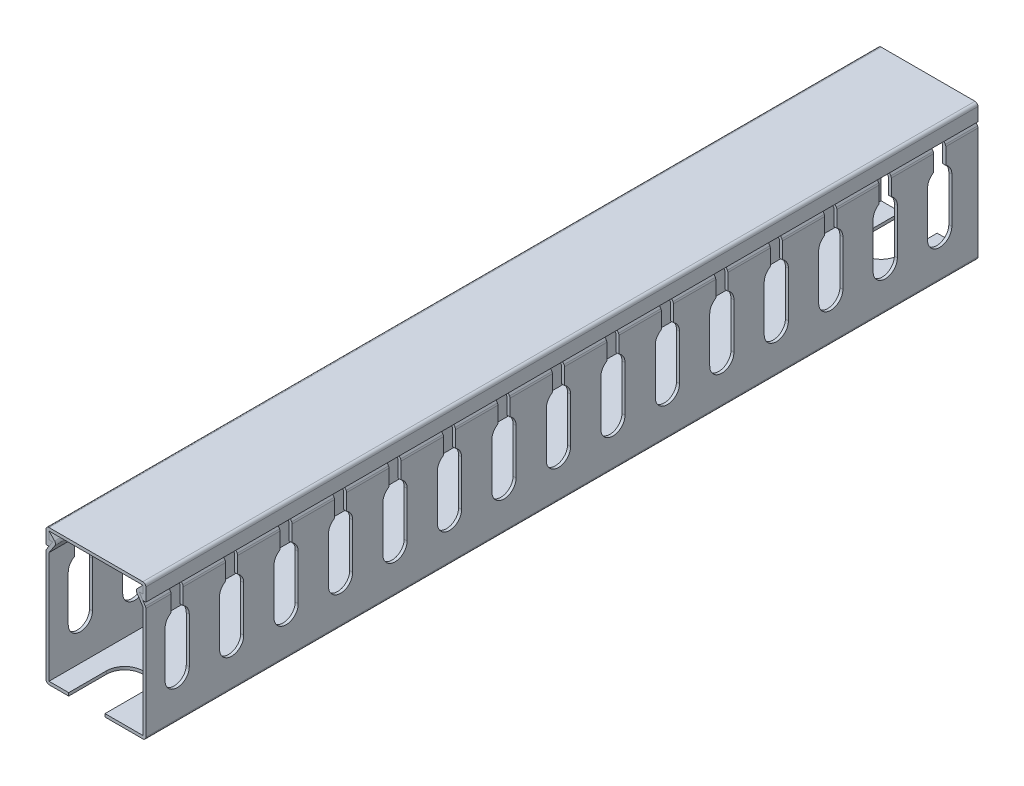
SolidWorks part; units mm, degrees
ref_plane "Front Plane" through (0, 0, 0) normal (0, 0, 1) x (1, 0, 0)
ref_plane "Top Plane" through (0, 0, 0) normal (0, 1, 0) x (1, 0, 0)
ref_plane "Right Plane" through (0, 0, 0) normal (1, 0, 0) x (0, 0, -1)
sketch "Sketch3" plane through (0, 0, 0) normal (0, 0, 1) x (1, 0, 0)
  line L234 (16.5, 37.8346) -> (16.5, 1)
  line L235 (16.3339, 38.3865) -> (14.281, 41.4887)
  line L236 (14.281, 41.4887) -> (15.5, 41.4887)
  line L237 (16.5, 39.6228) -> (16.5, 44)
  line L238 (16.5, 39.6228) -> (15.5158, 39.6228)
  line L239 (15.5, 41.4887) -> (15.5, 44)
  line L240 (15.5, 37.8346) -> (15.5, 1)
  line L241 (15.5, 37.8346) -> (13.5241, 40.8204)
  line L242 (13.6377, 42.0659) -> (15.5, 44)
  line L243 (-16.5, 37.8346) -> (-16.5, 1)
  line L244 (-16.3339, 38.3865) -> (-14.281, 41.4887)
  line L245 (-14.281, 41.4887) -> (-15.5, 41.4887)
  line L246 (-16.5, 39.6228) -> (-16.5, 44)
  line L247 (-16.5, 39.6228) -> (-15.5158, 39.6228)
  line L248 (-15.5, 41.4887) -> (-15.5, 44)
  line L249 (-15.5, 37.8346) -> (-15.5, 1)
  line L250 (-15.5, 37.8346) -> (-13.5241, 40.8204)
  line L251 (-13.6377, 42.0659) -> (-15.5, 44)
  line L252 (15.5, 0) -> (-15.5, 0)
  line L253 (15.5, 45) -> (-15.5, 45)
  line L254 (15.5, 1) -> (-15.5, 1)
  line L255 (15.5, 44) -> (-15.5, 44)
  arc A96 (16.5, 37.8346) -> (16.3339, 38.3865) centre (15.5, 37.8346) ccw
  arc A97 (13.6377, 42.0659) -> (13.5241, 40.8204) centre (14.358, 41.3723) ccw
  arc A98 (16.5, 44) -> (15.5, 45) centre (15.5, 44) ccw
  arc A99 (15.5, 0) -> (16.5, 1) centre (15.5, 1) ccw
  arc A100 (-16.3339, 38.3865) -> (-16.5, 37.8346) centre (-15.5, 37.8346) ccw
  arc A101 (-13.5241, 40.8204) -> (-13.6377, 42.0659) centre (-14.358, 41.3723) ccw
  arc A102 (-15.5, 45) -> (-16.5, 44) centre (-15.5, 44) ccw
  arc A103 (-16.5, 1) -> (-15.5, 0) centre (-15.5, 1) ccw
sketch "Sketch4" plane through (0, 0, 0) normal (0, 0, 1) x (1, 0, 0)
  line L0 (-15.5, 37.8346) -> (-15.5, 1)
  line L1 (-15.5, 1) -> (15.5, 1)
  line L2 (15.5, 1) -> (15.5, 37.8346)
  line L3 (15.5, 37.8346) -> (15.5, 1) construction
  line L4 (15.5, 37.8346) -> (13.5241, 40.8204)
  line L5 (13.6377, 42.0659) -> (15.5, 44)
  line L6 (15.5, 44) -> (15.5, 41.4887)
  line L7 (15.5, 41.4887) -> (14.281, 41.4887)
  line L8 (14.281, 41.4887) -> (16.3339, 38.3865)
  line L9 (16.5, 37.8346) -> (16.5, 1)
  line L10 (15.5, 0) -> (-15.5, 0)
  line L11 (-16.5, 1) -> (-16.5, 37.8346)
  line L12 (-16.3339, 38.3865) -> (-14.281, 41.4887)
  line L13 (-14.281, 41.4887) -> (-15.5, 41.4887)
  line L14 (-15.5, 41.4887) -> (-15.5, 44)
  line L15 (-15.5, 44) -> (-13.6377, 42.0659)
  line L16 (-13.5241, 40.8204) -> (-15.5, 37.8346)
  line L17 (-15.5, 37.8346) -> (-15.5055, 37.8438)
  arc A0 (13.5241, 40.8204) -> (13.6377, 42.0659) centre (14.358, 41.3723) cw
  arc A1 (16.3339, 38.3865) -> (16.5, 37.8346) centre (15.5, 37.8346) cw
  arc A2 (16.5, 1) -> (15.5, 0) centre (15.5, 1) cw
  arc A3 (-15.5, 0) -> (-16.5, 1) centre (-15.5, 1) cw
  arc A4 (-16.5, 37.8346) -> (-16.3339, 38.3865) centre (-15.5, 37.8346) cw
  arc A5 (-13.6377, 42.0659) -> (-13.5241, 40.8204) centre (-14.358, 41.3723) cw
extrude "Boss-Extrude1" add sketch "Sketch4" along normal mid plane 1700 contours A5 L15 L14 L13 L12 A4 L11 A3 L10 A2 L9 A1 L8 L7 L6 L5 A0 L4 L2 L1 L0 L16 region at (-16.05, 19.4173, 0)
sketch "Sketch5" plane through (0, 0, 0) normal (0, 0, 1) x (1, 0, 0)
  line L0 (-14.281, 41.4887) -> (-15.5158, 39.6228)
  line L1 (-15.5158, 39.6228) -> (-16.5, 39.6228)
  line L2 (-16.5, 39.6228) -> (-16.5, 44)
  line L3 (-15.5, 45) -> (15.5, 45)
  line L4 (16.5, 44) -> (16.5, 39.6228)
  line L5 (16.5, 39.6228) -> (15.5158, 39.6228)
  line L6 (15.5158, 39.6228) -> (14.281, 41.4887)
  line L7 (14.281, 41.4887) -> (15.5, 41.4887)
  line L8 (15.5, 41.4887) -> (15.5, 44)
  line L9 (15.5, 44) -> (-15.5, 44)
  line L10 (-15.5, 44) -> (-15.5, 41.4887)
  line L11 (-15.5, 41.4887) -> (-14.281, 41.4887)
  arc A0 (-16.5, 44) -> (-15.5, 45) centre (-15.5, 44) cw
  arc A1 (15.5, 45) -> (16.5, 44) centre (15.5, 44) cw
extrude "Boss-Extrude2" add sketch "Sketch5" along normal mid plane 1700 separate body
sketch "Sketch6" plane through (16.5, 0, 0) normal (1, 0, 0) x (0, 0, -1)
  line L0 (-839.65, 29) -> (-839.65, 14) construction
  line L1 (-835.65, 29) -> (-835.65, 14)
  line L2 (-843.65, 29) -> (-843.65, 14)
  line L3 (-850, 0) -> (850, 0) construction
  line L4 (-850, 37.8346) -> (-850, 1) construction
  line L6 (-841.65, 44) -> (-837.65, 44)
  line L7 (-841.65, 44) -> (-841.65, 32.4641)
  line L9 (-837.65, 44) -> (-837.65, 32.4641)
  line L10 (-850, 44) -> (850, 44) construction
  arc A0 (-835.65, 29) -> (-837.65, 32.4641) centre (-839.65, 29) ccw
  arc A1 (-843.65, 14) -> (-835.65, 14) centre (-839.65, 14) ccw
  arc A2 (-841.65, 32.4641) -> (-843.65, 29) centre (-839.65, 29) ccw
  dimension "D4" = 4
  dimension "D1" = 15
  dimension "D2" = 14
  dimension "D3" = 10.35
  dimension "D5" = 4
  dimension "D6" = 2
extrude "Cut-Extrude1" cut sketch "Sketch6" against normal through all
pattern_linear "LPattern1" count 94 spacing 18 along (0, 0, -1) of "Cut-Extrude1"
sketch "Sketch7" plane through (0, 45, 0) normal (0, 1, 0) x (1, 0, 0)
  line L1 (47.8654, -850) -> (-52.8923, -850)
  line L2 (47.8654, -850) -> (47.8654, -575)
  line L3 (47.8654, -575) -> (-52.8923, -575)
  line L4 (-52.8923, -850) -> (-52.8923, -575)
  line L5 (125.8279, -883.2089) -> (-418.2435, -883.2089)
  line L6 (125.8279, -883.2089) -> (125.8279, 1066.7187)
  line L7 (125.8279, 1066.7187) -> (-418.2435, 1066.7187)
  line L8 (-418.2435, -883.2089) -> (-418.2435, 1066.7187)
  dimension "D1" = 275
extrude "Cut-Extrude2" cut sketch "Sketch7" against normal blind 398
sketch "Sketch8" plane through (0, 0, 0) normal (0, -1, 0) x (1, 0, 0)
  line L0 (15.5, 850) -> (-15.5, 850) construction
  line L1 (15.5, 850) -> (15.5, 575) construction
  line L2 (-9, 837.5) -> (-9, 850)
  line L3 (-9, 850) -> (3, 850)
  line L4 (3, 850) -> (3, 837.5)
  arc A0 (-9, 837.5) -> (3, 837.5) centre (-3, 837.5) ccw
  dimension "D1" = 12.5
  dimension "D2" = 18.5
extrude "Cut-Extrude3" cut sketch "Sketch8" against normal blind 10
sketch "Sketch9" plane through (0, 0, 0) normal (0, -1, 0) x (1, 0, 0)
  line L0 (-15.5, 575) -> (15.5, 575) construction
  line L1 (-9, 587.5) -> (-9, 575)
  line L2 (-9, 575) -> (3, 575)
  line L3 (3, 575) -> (2.9888, 587.133)
  arc A0 (2.9888, 587.133) -> (-9, 587.5) centre (-3, 587.5) ccw
  dimension "D1" = 18.5
  dimension "D2" = 12.5
extrude "Cut-Extrude4" cut sketch "Sketch9" against normal blind 10
